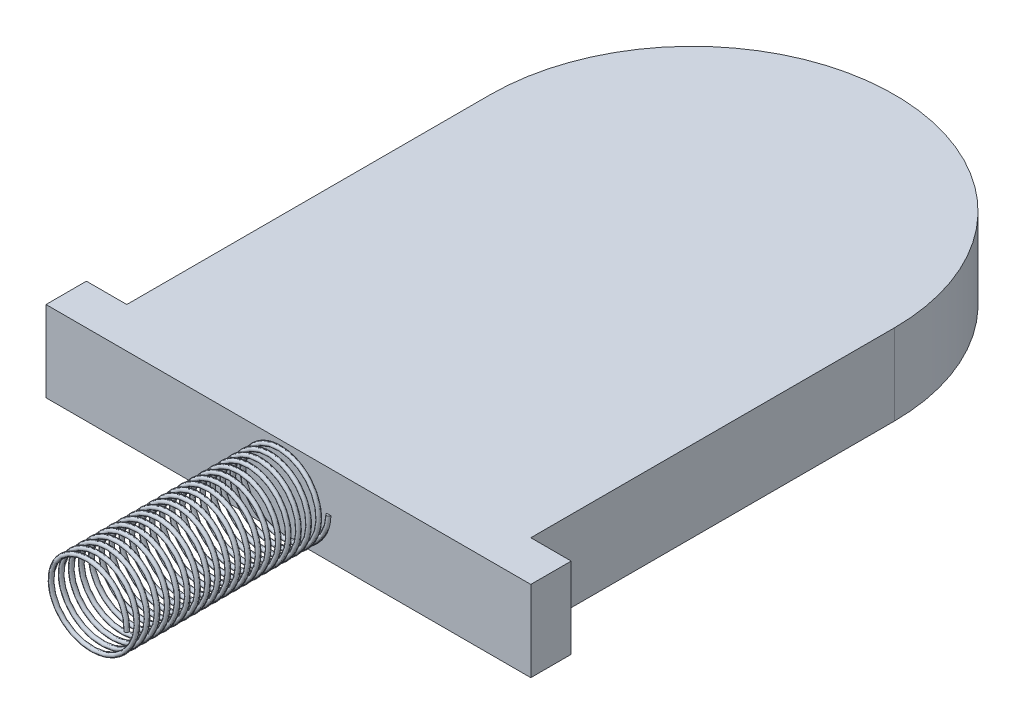
SolidWorks part; units mm, degrees
ref_plane "前视基准面" through (0, 0, 0) normal (0, 0, 1) x (1, 0, 0)
ref_plane "上视基准面" through (0, 0, 0) normal (0, 1, 0) x (1, 0, 0)
ref_plane "右视基准面" through (0, 0, 0) normal (1, 0, 0) x (0, 0, -1)
sketch "草图1" plane through (0, 0, 0) normal (0, 1, 0) x (1, 0, 0)
  line L1 (-1, 1) -> (1, 1)
  line L2 (-1, 1) -> (-1, -1)
  line L3 (-1, -1) -> (1, -1)
  line L4 (1, 1) -> (1, -1)
  line L5 (-1, 1) -> (1, -1) construction
  line L6 (-1, -1) -> (1, 1) construction
  arc A0 (-1, 1) -> (1, 1) centre (0, 1) cw
  point P0 (0, 0)
  dimension "D1" = 2
  dimension "D2" = 2
extrude "凸台-拉伸1" add sketch "草图1" along normal blind 0.4 contours A0 L1 | L4 L1 L2 L3
sketch "草图2" plane through (0, 0, 1) normal (0, 0, 1) x (1, 0, 0)
  circle A0 centre (0, 0.2) radius 0.2
  dimension "D1" = 0.4
curve "螺旋线/涡状线1" pitch 0.05 height 1 turns 20
sketch "草图3" plane through (0, 0, 1) normal (0, 0, 1) x (1, 0, 0)
  line L0 (-1, 0.2) -> (1, 0.2)
  line L1 (-1, 0.4) -> (-1, 0) construction
  line L2 (1, 0.4) -> (1, 0) construction
ref_plane "基准面1" through (0, 0.2, 0) normal (0, 1, 0) x (-1, 0, 0)
sketch "草图4" plane through (0, 0.2, 0) normal (0, 1, 0) x (-1, 0, 0)
  line L1 (1, 1) -> (-1, 1) construction
  circle A0 centre (-0.2, 1) radius 0.01
  dimension "D1" = 0.02
sweep "扫描1" add profiles "草图4" path "螺旋线/涡状线1"
sketch "草图5" plane through (1, 0, 0) normal (1, 0, 0) x (0, 0, -1)
  line L0 (1, 0.4) -> (-1, 0.4) construction
  line L1 (-1, 0) -> (-0.8, 0)
  line L2 (-1, 0) -> (-1, 0.4)
  line L3 (-1, 0.4) -> (-0.8, 0.4)
  line L4 (-0.8, 0) -> (-0.8, 0.4)
  dimension "D1" = 0.2
extrude "凸台-拉伸2" add sketch "草图5" along normal blind 0.2 and the other way blind 2.2
